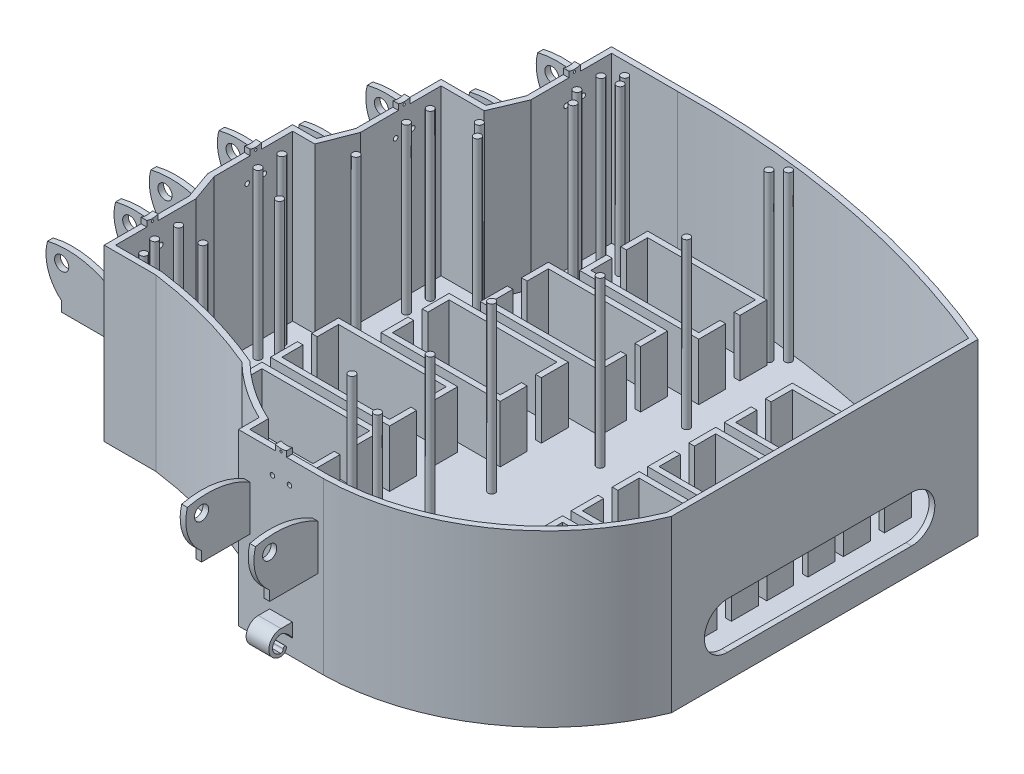
SolidWorks part; units mm, degrees
ref_plane "Front Plane" through (0, 0, 0) normal (0, 0, 1) x (1, 0, 0)
ref_plane "Top Plane" through (0, 0, 0) normal (0, 1, 0) x (1, 0, 0)
ref_plane "Right Plane" through (0, 0, 0) normal (1, 0, 0) x (0, 0, -1)
ref_plane "Palm Side Plane" through (0, 38.1, 0) normal (0, 1, 0) x (1, 0, 0)
ref_plane "Left Side Plane" through (0, 0, 63.5) normal (0, 0, 1) x (1, 0, 0)
ref_plane "Top Side Plane" through (-69.85, 0, 0) normal (1, 0, 0) x (0, 0, -1)
ref_plane "Wrist Plane" through (62.9138, 0, 0) normal (1, 0, 0) x (0, 0, -1)
sketch "Hand Direction Arrow" plane through (0, 38.1, 0) normal (0, 1, 0) x (1, 0, 0)
  line L0 (49.8191, -114.0829) -> (-36.738, -114.0829) construction
  line L1 (-36.738, -114.0829) -> (-22.4792, -131.555) construction
  line L2 (-36.738, -114.0829) -> (-22.4792, -99.8241) construction
sketch "Sketch2" plane through (0, 0, 0) normal (0, 1, 0) x (1, 0, 0)
  line L5 (-69.85, -63.5) -> (69.85, 63.5) construction
  line L6 (-69.85, 63.5) -> (69.85, -63.5) construction
  line L7 (-20.7784, 52.7587) -> (-36.189, 52.7587)
  line L8 (-36.189, 52.7587) -> (-36.189, 33.7087)
  line L9 (-42.9594, -42.4913) -> (-54.5039, -42.4913)
  line L10 (-54.5039, -42.4913) -> (-54.5039, -23.4413)
  line L11 (-54.5039, -23.4413) -> (-56.7676, -17.0913)
  line L12 (-51.4171, 1.9587) -> (-48.9477, 8.3087)
  line L14 (-56.7676, -17.0913) -> (-56.7676, 1.9587)
  line L15 (-56.7676, 1.9587) -> (-51.4171, 1.9587)
  line L16 (-38.8642, 27.3587) -> (-36.189, 33.7087)
  line L19 (15.3118, -63.2103) -> (-3.7382, -63.2103)
  line L20 (-3.7382, -63.2103) -> (-3.7382, -58.593)
  line L21 (61.5724, -31.5884) -> (61.5724, 37.0553)
  line L22 (-48.9477, 8.3087) -> (-48.9477, 27.3587)
  line L23 (-48.9477, 27.3587) -> (-38.8642, 27.3587)
  arc A0 (61.5724, 37.0553) -> (-20.7784, 52.7587) centre (-16.6219, -149.2259) ccw
  arc A2 (-42.9594, -42.4913) -> (-16.4221, -49.7553) centre (-56.8306, -145.2734) cw
  arc A5 (-3.7382, -58.593) -> (-16.4221, -49.7553) centre (16.7508, -15.6666) cw
  arc A6 (15.3118, -63.2103) -> (61.5724, -31.5884) centre (14.5642, -12.4678) ccw
  point P0 (0, 0)
  dimension "D1" = 19.05
  dimension "D2" = 19.05
  dimension "D3" = 19.05
  dimension "D4" = 19.05
  dimension "D5" = 19.05
  dimension "D6" = 6.35
  dimension "D7" = 6.35
extrude "Boss-Extrude1" add sketch "Sketch2" along normal blind 38.1
sketch "Sketch3" plane through (0, 38.1, 0) normal (0, 1, 0) x (1, 0, 0)
  line L5 (-68.58, -62.23) -> (68.58, 62.23) construction
  line L6 (-68.58, 62.23) -> (68.58, -62.23) construction
  line L7 (-20.1932, 51.4997) -> (-34.919, 51.4997)
  line L8 (-34.919, 51.4997) -> (-34.919, 33.4521)
  line L10 (-36.189, 52.7587) -> (-36.189, 33.7087) construction
  line L11 (-54.5039, -23.4413) -> (-54.5039, -42.4913) construction
  line L12 (-42.8744, -41.2213) -> (-53.2339, -41.2213)
  line L13 (-53.2339, -41.2213) -> (-53.2339, -23.2217)
  line L18 (-55.4976, -16.8717) -> (-55.4976, 0.6887)
  line L19 (-55.4976, 0.6887) -> (-50.5484, 0.6887)
  line L22 (-56.7676, 1.9587) -> (-56.7676, -17.0913) construction
  line L23 (-51.4171, 1.9587) -> (-56.7676, 1.9587) construction
  line L24 (-47.6777, 8.0704) -> (-47.6777, 26.0887)
  line L25 (-47.6777, 26.0887) -> (-38.0211, 26.0887)
  line L26 (-48.9477, 27.3587) -> (-48.9477, 8.3087) construction
  line L27 (-38.8642, 27.3587) -> (-48.9477, 27.3587) construction
  line L28 (-38.0211, 26.0887) -> (-34.919, 33.4521)
  line L29 (-36.189, 33.7087) -> (-38.8642, 27.3587) construction
  line L30 (-50.5484, 0.6887) -> (-47.6777, 8.0704)
  line L31 (-54.5039, -42.4913) -> (-42.9594, -42.4913) construction
  line L32 (-53.2339, -23.2217) -> (-55.4976, -16.8717)
  line L33 (-56.7676, -17.0913) -> (-54.5039, -23.4413) construction
  line L34 (-48.9477, 8.3087) -> (-51.4171, 1.9587) construction
  line L35 (15.3312, -61.9403) -> (-2.4682, -61.9403)
  line L36 (-2.4682, -61.9403) -> (-2.4682, -57.7843)
  line L37 (-3.7382, -58.593) -> (-3.7382, -63.2103) construction
  line L38 (-3.7382, -63.2103) -> (15.3118, -63.2103) construction
  line L39 (60.3024, -31.3395) -> (60.3024, 36.2091)
  line L40 (61.5724, -31.5884) -> (61.5724, 37.0553) construction
  arc A1 (-20.1932, 51.4997) -> (60.3024, 36.2091) centre (-16.6219, -149.2259) cw
  arc A4 (61.5724, 37.0553) -> (-20.7784, 52.7587) centre (-16.6219, -149.2259) ccw construction
  arc A5 (15.3118, -63.2103) -> (61.5724, -31.5884) centre (14.5642, -12.4678) ccw construction
  arc A8 (-42.8744, -41.2213) -> (-15.7053, -48.6798) centre (-56.8306, -145.2734) cw
  arc A9 (-16.4221, -49.7553) -> (-42.9594, -42.4913) centre (-56.8306, -145.2734) ccw construction
  arc A12 (15.3312, -61.9403) -> (60.3024, -31.3395) centre (14.5642, -12.4678) ccw
  arc A13 (-2.4682, -57.7843) -> (-15.7053, -48.6798) centre (16.7508, -15.6666) cw
  arc A14 (-16.4221, -49.7553) -> (-3.7382, -58.593) centre (16.7508, -15.6666) ccw construction
  point P0 (0, 0)
  point P6 (-45.5127, -25.7954)
  point P29 (-45.5127, -25.7954)
  point P52 (-54.0923, 1.9587)
  dimension "D2" = 1.27
  dimension "D3" = 1.27
  dimension "D5" = 1.27
  dimension "D6" = 1.27
  dimension "D8" = 1.27
  dimension "D4" = 1.27
  dimension "D7" = 1.27
  dimension "D9" = 1.27
  dimension "D10" = 1.27
  dimension "D11" = 1.27
  dimension "D12" = 1.27
  dimension "D13" = 1.27
  dimension "D14" = 1.27
  dimension "D15" = 1.27
  dimension "D16" = 1.27
  dimension "D17" = 1.27
extrude "Cut-Extrude1" cut sketch "Sketch3" against normal blind 36.83
sketch "Sketch6" plane through (0, 0, 0) normal (0, 1, 0) x (1, 0, 0)
  line L0 (-38.2959, -32.597) -> (-37.0259, -32.597)
  line L5 (-63.3937, -68.1577) -> (73.7663, 56.3023) construction
  line L6 (-64.5742, 57.9506) -> (72.5858, -66.5094) construction
  line L7 (-12.8959, -37.3595) -> (-37.0259, -37.3595)
  line L8 (-12.8959, -37.3595) -> (-12.8959, -32.597)
  line L9 (-12.8959, -24.6595) -> (-37.0259, -24.6595)
  line L10 (-37.0259, -37.3595) -> (-37.0259, -32.597)
  line L11 (-12.8959, -37.3595) -> (-37.0259, -24.6595) construction
  line L12 (-12.8959, -24.6595) -> (-37.0259, -37.3595) construction
  line L13 (-11.6259, -38.6295) -> (-38.2959, -38.6295)
  line L14 (-11.6259, -38.6295) -> (-11.6259, -32.597)
  line L15 (-11.6259, -23.3895) -> (-38.2959, -23.3895)
  line L16 (-38.2959, -38.6295) -> (-38.2959, -32.597)
  line L17 (-11.6259, -38.6295) -> (-38.2959, -23.3895) construction
  line L18 (-11.6259, -23.3895) -> (-38.2959, -38.6295) construction
  line L19 (-38.2959, -29.422) -> (-37.0259, -29.422)
  line L20 (-38.2959, -29.422) -> (-38.2959, -23.3895)
  line L21 (-37.0259, -29.422) -> (-37.0259, -24.6595)
  line L22 (-12.8959, -32.597) -> (-11.6259, -32.597)
  line L23 (-12.8959, -29.422) -> (-11.6259, -29.422)
  line L24 (-12.8959, -29.422) -> (-12.8959, -24.6595)
  line L25 (-11.6259, -29.422) -> (-11.6259, -23.3895)
  point P0 (5.5042, -5.6391)
  point P6 (-24.9609, -31.0095)
  point P29 (-24.9609, -31.0095)
  dimension "D6" = 1.27
  dimension "D7" = 1.27
  dimension "D9" = 12.7
  dimension "D10" = 24.13
  dimension "D11" = 4.7625
  dimension "D12" = 4.7625
  dimension "D13" = 4.7625
  dimension "D14" = 4.7625
extrude "Boss-Extrude2" add sketch "Sketch6" along normal blind 13.97
sketch "Sketch7" plane through (0, 0, 0) normal (0, 1, 0) x (1, 0, 0)
  line L0 (-38.2959, -15.452) -> (-37.0259, -15.452)
  line L5 (-11.6259, -23.3895) -> (-38.2959, -23.3895) construction
  line L6 (-38.2959, -23.3895) -> (-38.2959, -29.422) construction
  line L7 (-12.8959, -20.2145) -> (-37.0259, -20.2145)
  line L8 (-12.8959, -20.2145) -> (-12.8959, -15.452)
  line L9 (-12.8959, -7.5145) -> (-37.0259, -7.5145)
  line L10 (-37.0259, -20.2145) -> (-37.0259, -15.452)
  line L11 (-12.8959, -20.2145) -> (-37.0259, -7.5145) construction
  line L12 (-12.8959, -7.5145) -> (-37.0259, -20.2145) construction
  line L13 (-11.6259, -21.4845) -> (-38.2959, -21.4845)
  line L14 (-11.6259, -21.4845) -> (-11.6259, -15.452)
  line L15 (-11.6259, -6.2445) -> (-38.2959, -6.2445)
  line L16 (-38.2959, -21.4845) -> (-38.2959, -15.452)
  line L17 (-11.6259, -21.4845) -> (-38.2959, -6.2445) construction
  line L18 (-11.6259, -6.2445) -> (-38.2959, -21.4845) construction
  line L19 (-38.2959, -12.277) -> (-37.0259, -12.277)
  line L20 (-38.2959, -12.277) -> (-38.2959, -6.2445)
  line L21 (-37.0259, -12.277) -> (-37.0259, -7.5145)
  line L22 (-12.8959, -15.452) -> (-11.6259, -15.452)
  line L23 (-12.8959, -12.277) -> (-11.6259, -12.277)
  line L24 (-12.8959, -12.277) -> (-12.8959, -7.5145)
  line L25 (-11.6259, -12.277) -> (-11.6259, -6.2445)
  point P0 (-14.8998, -5.4903)
  point P6 (-24.9609, -13.8645)
  point P29 (-24.9609, -13.8645)
  dimension "D2" = 1.905
  dimension "D3" = 0
  dimension "D6" = 1.27
  dimension "D7" = 1.27
  dimension "D9" = 12.7
  dimension "D10" = 24.13
  dimension "D11" = 4.7625
  dimension "D12" = 4.7625
  dimension "D13" = 4.7625
  dimension "D14" = 4.7625
extrude "Boss-Extrude3" add sketch "Sketch7" along normal blind 13.97
sketch "Sketch15" plane through (0, 0, 0) normal (0, -1, 0) x (1, 0, 0)
  line L0 (-30.6759, -4.868) -> (-29.4059, -4.868)
  line L5 (-11.6259, 6.2445) -> (-38.2959, 6.2445) construction
  line L6 (-38.2959, 6.2445) -> (-38.2959, 12.277) construction
  line L7 (-5.2759, -9.6305) -> (-29.4059, -9.6305)
  line L8 (-5.2759, -9.6305) -> (-5.2759, -4.868)
  line L9 (-5.2759, 3.0695) -> (-29.4059, 3.0695)
  line L10 (-29.4059, -9.6305) -> (-29.4059, -4.868)
  line L11 (-5.2759, -9.6305) -> (-29.4059, 3.0695) construction
  line L12 (-5.2759, 3.0695) -> (-29.4059, -9.6305) construction
  line L13 (-4.0059, -10.9005) -> (-30.6759, -10.9005)
  line L14 (-4.0059, -10.9005) -> (-4.0059, -4.868)
  line L15 (-4.0059, 4.3395) -> (-30.6759, 4.3395)
  line L16 (-30.6759, -10.9005) -> (-30.6759, -4.868)
  line L17 (-4.0059, -10.9005) -> (-30.6759, 4.3395) construction
  line L18 (-4.0059, 4.3395) -> (-30.6759, -10.9005) construction
  line L19 (-30.6759, -1.693) -> (-29.4059, -1.693)
  line L20 (-30.6759, -1.693) -> (-30.6759, 4.3395)
  line L21 (-29.4059, -1.693) -> (-29.4059, 3.0695)
  line L22 (-5.2759, -4.868) -> (-4.0059, -4.868)
  line L23 (-5.2759, -1.693) -> (-4.0059, -1.693)
  line L24 (-5.2759, -1.693) -> (-5.2759, 3.0695)
  line L25 (-4.0059, -1.693) -> (-4.0059, 4.3395)
  point P0 (-6.5637, 8.998)
  point P6 (-17.3409, -3.2805)
  point P29 (-17.3409, -3.2805)
  dimension "D2" = 1.905
  dimension "D3" = 7.62
  dimension "D6" = 1.27
  dimension "D7" = 1.27
  dimension "D9" = 12.7
  dimension "D10" = 24.13
  dimension "D11" = 4.7625
  dimension "D12" = 4.7625
  dimension "D13" = 4.7625
  dimension "D14" = 4.7625
extrude "Boss-Extrude4" add sketch "Sketch15" against normal blind 13.97
sketch "Sketch16" plane through (0, 0, 0) normal (0, -1, 0) x (1, 0, 0)
  line L0 (-25.5959, -22.013) -> (-24.3259, -22.013)
  line L5 (-30.6759, -10.9005) -> (-4.0059, -10.9005) construction
  line L6 (-30.6759, -4.868) -> (-30.6759, -10.9005) construction
  line L7 (-0.1959, -26.7755) -> (-24.3259, -26.7755)
  line L8 (-0.1959, -26.7755) -> (-0.1959, -22.013)
  line L9 (-0.1959, -14.0755) -> (-24.3259, -14.0755)
  line L10 (-24.3259, -26.7755) -> (-24.3259, -22.013)
  line L11 (-0.1959, -26.7755) -> (-24.3259, -14.0755) construction
  line L12 (-0.1959, -14.0755) -> (-24.3259, -26.7755) construction
  line L13 (1.0741, -28.0455) -> (-25.5959, -28.0455)
  line L14 (1.0741, -28.0455) -> (1.0741, -22.013)
  line L15 (1.0741, -12.8055) -> (-25.5959, -12.8055)
  line L16 (-25.5959, -28.0455) -> (-25.5959, -22.013)
  line L17 (1.0741, -28.0455) -> (-25.5959, -12.8055) construction
  line L18 (1.0741, -12.8055) -> (-25.5959, -28.0455) construction
  line L19 (-25.5959, -18.838) -> (-24.3259, -18.838)
  line L20 (-25.5959, -18.838) -> (-25.5959, -12.8055)
  line L21 (-24.3259, -18.838) -> (-24.3259, -14.0755)
  line L22 (-0.1959, -22.013) -> (1.0741, -22.013)
  line L23 (-0.1959, -18.838) -> (1.0741, -18.838)
  line L24 (-0.1959, -18.838) -> (-0.1959, -14.0755)
  line L25 (1.0741, -18.838) -> (1.0741, -12.8055)
  point P0 (1.9027, -6.9539)
  point P6 (-12.2609, -20.4255)
  point P29 (-12.2609, -20.4255)
  dimension "D2" = 1.905
  dimension "D3" = 5.08
  dimension "D6" = 1.27
  dimension "D7" = 1.27
  dimension "D9" = 12.7
  dimension "D10" = 24.13
  dimension "D11" = 4.7625
  dimension "D12" = 4.7625
  dimension "D13" = 4.7625
  dimension "D14" = 4.7625
extrude "Boss-Extrude5" add sketch "Sketch16" against normal blind 13.97
sketch "Sketch17" plane through (0, 0, 0) normal (0, -1, 0) x (1, 0, 0)
  line L0 (-20.5159, -39.158) -> (-19.2459, -39.158)
  line L5 (-25.5959, -28.0455) -> (1.0741, -28.0455) construction
  line L6 (-25.5959, -22.013) -> (-25.5959, -28.0455) construction
  line L7 (4.8841, -43.9205) -> (-19.2459, -43.9205)
  line L8 (4.8841, -43.9205) -> (4.8841, -39.158)
  line L9 (4.8841, -31.2205) -> (-19.2459, -31.2205)
  line L10 (-19.2459, -43.9205) -> (-19.2459, -39.158)
  line L11 (4.8841, -43.9205) -> (-19.2459, -31.2205) construction
  line L12 (4.8841, -31.2205) -> (-19.2459, -43.9205) construction
  line L13 (6.1541, -45.1905) -> (-20.5159, -45.1905)
  line L14 (6.1541, -45.1905) -> (6.1541, -39.158)
  line L15 (6.1541, -29.9505) -> (-20.5159, -29.9505)
  line L16 (-20.5159, -45.1905) -> (-20.5159, -39.158)
  line L17 (6.1541, -45.1905) -> (-20.5159, -29.9505) construction
  line L18 (6.1541, -29.9505) -> (-20.5159, -45.1905) construction
  line L19 (-20.5159, -35.983) -> (-19.2459, -35.983)
  line L20 (-20.5159, -35.983) -> (-20.5159, -29.9505)
  line L21 (-19.2459, -35.983) -> (-19.2459, -31.2205)
  line L22 (4.8841, -39.158) -> (6.1541, -39.158)
  line L23 (4.8841, -35.983) -> (6.1541, -35.983)
  line L24 (4.8841, -35.983) -> (4.8841, -31.2205)
  line L25 (6.1541, -35.983) -> (6.1541, -29.9505)
  point P0 (6.1079, -24.4951)
  point P6 (-7.1809, -37.5705)
  point P29 (-7.1809, -37.5705)
  dimension "D2" = 1.905
  dimension "D3" = 5.08
  dimension "D6" = 1.27
  dimension "D7" = 1.27
  dimension "D9" = 12.7
  dimension "D10" = 24.13
  dimension "D11" = 4.7625
  dimension "D12" = 4.7625
  dimension "D13" = 4.7625
  dimension "D14" = 4.7625
extrude "Boss-Extrude6" add sketch "Sketch17" against normal blind 13.97
sketch "Sketch18" plane through (0, 0, 0) normal (0, -1, 0) x (1, 0, 0)
  line L0 (14.981, 42.6949) -> (16.251, 42.6949)
  line L7 (40.381, 37.9324) -> (16.251, 37.9324)
  line L8 (40.381, 37.9324) -> (40.381, 42.6949)
  line L9 (40.381, 50.6324) -> (16.251, 50.6324)
  line L10 (16.251, 37.9324) -> (16.251, 42.6949)
  line L11 (40.381, 37.9324) -> (16.251, 50.6324) construction
  line L12 (40.381, 50.6324) -> (16.251, 37.9324) construction
  line L13 (41.651, 36.6624) -> (14.981, 36.6624)
  line L14 (41.651, 36.6624) -> (41.651, 42.6949)
  line L15 (41.651, 51.9024) -> (14.981, 51.9024)
  line L16 (14.981, 36.6624) -> (14.981, 42.6949)
  line L17 (41.651, 36.6624) -> (14.981, 51.9024) construction
  line L18 (41.651, 51.9024) -> (14.981, 36.6624) construction
  line L19 (14.981, 45.8699) -> (16.251, 45.8699)
  line L20 (14.981, 45.8699) -> (14.981, 51.9024)
  line L21 (16.251, 45.8699) -> (16.251, 50.6324)
  line L22 (40.381, 42.6949) -> (41.651, 42.6949)
  line L23 (40.381, 45.8699) -> (41.651, 45.8699)
  line L24 (40.381, 45.8699) -> (40.381, 50.6324)
  line L25 (41.651, 45.8699) -> (41.651, 51.9024)
  point P0 (43.5107, 54.1626)
  point P6 (28.316, 44.2824)
  point P29 (28.316, 44.2824)
  dimension "D6" = 1.27
  dimension "D7" = 1.27
  dimension "D9" = 12.7
  dimension "D10" = 24.13
  dimension "D11" = 4.7625
  dimension "D12" = 4.7625
  dimension "D13" = 4.7625
  dimension "D14" = 4.7625
extrude "Boss-Extrude7" add sketch "Sketch18" against normal blind 13.97
sketch "Sketch19" plane through (0, 0, 0) normal (0, -1, 0) x (1, 0, 0)
  line L0 (25.141, 25.5499) -> (26.411, 25.5499)
  line L5 (14.981, 36.6624) -> (41.651, 36.6624) construction
  line L6 (14.981, 42.6949) -> (14.981, 36.6624) construction
  line L7 (50.541, 20.7874) -> (26.411, 20.7874)
  line L8 (50.541, 20.7874) -> (50.541, 25.5499)
  line L9 (50.541, 33.4874) -> (26.411, 33.4874)
  line L10 (26.411, 20.7874) -> (26.411, 25.5499)
  line L11 (50.541, 20.7874) -> (26.411, 33.4874) construction
  line L12 (50.541, 33.4874) -> (26.411, 20.7874) construction
  line L13 (51.811, 19.5174) -> (25.141, 19.5174)
  line L14 (51.811, 19.5174) -> (51.811, 25.5499)
  line L15 (51.811, 34.7574) -> (25.141, 34.7574)
  line L16 (25.141, 19.5174) -> (25.141, 25.5499)
  line L17 (51.811, 19.5174) -> (25.141, 34.7574) construction
  line L18 (51.811, 34.7574) -> (25.141, 19.5174) construction
  line L19 (25.141, 28.7249) -> (26.411, 28.7249)
  line L20 (25.141, 28.7249) -> (25.141, 34.7574)
  line L21 (26.411, 28.7249) -> (26.411, 33.4874)
  line L22 (50.541, 25.5499) -> (51.811, 25.5499)
  line L23 (50.541, 28.7249) -> (51.811, 28.7249)
  line L24 (50.541, 28.7249) -> (50.541, 33.4874)
  line L25 (51.811, 28.7249) -> (51.811, 34.7574)
  point P0 (52.4146, 37.8023)
  point P6 (38.476, 27.1374)
  point P29 (38.476, 27.1374)
  dimension "D2" = 1.905
  dimension "D3" = 10.16
  dimension "D6" = 1.27
  dimension "D7" = 1.27
  dimension "D9" = 12.7
  dimension "D10" = 24.13
  dimension "D11" = 4.7625
  dimension "D12" = 4.7625
  dimension "D13" = 4.7625
  dimension "D14" = 4.7625
extrude "Boss-Extrude8" add sketch "Sketch19" against normal blind 13.97
sketch "Sketch20" plane through (0, 0, 0) normal (0, -1, 0) x (1, 0, 0)
  line L0 (25.141, 8.4049) -> (26.411, 8.4049)
  line L5 (25.141, 25.5499) -> (25.141, 19.5174) construction
  line L6 (25.141, 19.5174) -> (51.811, 19.5174) construction
  line L7 (50.541, 3.6424) -> (26.411, 3.6424)
  line L8 (50.541, 3.6424) -> (50.541, 8.4049)
  line L9 (50.541, 16.3424) -> (26.411, 16.3424)
  line L10 (26.411, 3.6424) -> (26.411, 8.4049)
  line L11 (50.541, 3.6424) -> (26.411, 16.3424) construction
  line L12 (50.541, 16.3424) -> (26.411, 3.6424) construction
  line L13 (51.811, 2.3724) -> (25.141, 2.3724)
  line L14 (51.811, 2.3724) -> (51.811, 8.4049)
  line L15 (51.811, 17.6124) -> (25.141, 17.6124)
  line L16 (25.141, 2.3724) -> (25.141, 8.4049)
  line L17 (51.811, 2.3724) -> (25.141, 17.6124) construction
  line L18 (51.811, 17.6124) -> (25.141, 2.3724) construction
  line L19 (25.141, 11.5799) -> (26.411, 11.5799)
  line L20 (25.141, 11.5799) -> (25.141, 17.6124)
  line L21 (26.411, 11.5799) -> (26.411, 16.3424)
  line L22 (50.541, 8.4049) -> (51.811, 8.4049)
  line L23 (50.541, 11.5799) -> (51.811, 11.5799)
  line L24 (50.541, 11.5799) -> (50.541, 16.3424)
  line L25 (51.811, 11.5799) -> (51.811, 17.6124)
  point P0 (54.8865, 20.8211)
  point P6 (38.476, 9.9924)
  point P29 (38.476, 9.9924)
  dimension "D2" = 0
  dimension "D3" = 1.905
  dimension "D6" = 1.27
  dimension "D7" = 1.27
  dimension "D9" = 12.7
  dimension "D10" = 24.13
  dimension "D11" = 4.7625
  dimension "D12" = 4.7625
  dimension "D13" = 4.7625
  dimension "D14" = 4.7625
extrude "Boss-Extrude9" add sketch "Sketch20" against normal blind 13.97
sketch "Sketch21" plane through (0, 0, 0) normal (0, -1, 0) x (1, 0, 0)
  line L0 (25.141, -8.7401) -> (26.411, -8.7401)
  line L5 (25.141, 2.3724) -> (51.811, 2.3724) construction
  line L6 (25.141, 8.4049) -> (25.141, 2.3724) construction
  line L7 (50.541, -13.5026) -> (26.411, -13.5026)
  line L8 (50.541, -13.5026) -> (50.541, -8.7401)
  line L9 (50.541, -0.8026) -> (26.411, -0.8026)
  line L10 (26.411, -13.5026) -> (26.411, -8.7401)
  line L11 (50.541, -13.5026) -> (26.411, -0.8026) construction
  line L12 (50.541, -0.8026) -> (26.411, -13.5026) construction
  line L13 (51.811, -14.7726) -> (25.141, -14.7726)
  line L14 (51.811, -14.7726) -> (51.811, -8.7401)
  line L15 (51.811, 0.4674) -> (25.141, 0.4674)
  line L16 (25.141, -14.7726) -> (25.141, -8.7401)
  line L17 (51.811, -14.7726) -> (25.141, 0.4674) construction
  line L18 (51.811, 0.4674) -> (25.141, -14.7726) construction
  line L19 (25.141, -5.5651) -> (26.411, -5.5651)
  line L20 (25.141, -5.5651) -> (25.141, 0.4674)
  line L21 (26.411, -5.5651) -> (26.411, -0.8026)
  line L22 (50.541, -8.7401) -> (51.811, -8.7401)
  line L23 (50.541, -5.5651) -> (51.811, -5.5651)
  line L24 (50.541, -5.5651) -> (50.541, -0.8026)
  line L25 (51.811, -5.5651) -> (51.811, 0.4674)
  point P0 (52.1156, 3.8173)
  point P6 (38.476, -7.1526)
  point P29 (38.476, -7.1526)
  dimension "D2" = 1.905
  dimension "D3" = 0
  dimension "D6" = 1.27
  dimension "D7" = 1.27
  dimension "D9" = 12.7
  dimension "D10" = 24.13
  dimension "D11" = 4.7625
  dimension "D12" = 4.7625
  dimension "D13" = 4.7625
  dimension "D14" = 4.7625
extrude "Boss-Extrude10" add sketch "Sketch21" against normal blind 13.97
sketch "Sketch22" plane through (0, 0, 0) normal (0, -1, 0) x (1, 0, 0)
  line L0 (25.141, -25.8851) -> (26.411, -25.8851)
  line L5 (25.141, -14.7726) -> (51.811, -14.7726) construction
  line L6 (25.141, -8.7401) -> (25.141, -14.7726) construction
  line L7 (50.541, -30.6476) -> (26.411, -30.6476)
  line L8 (50.541, -30.6476) -> (50.541, -25.8851)
  line L9 (50.541, -17.9476) -> (26.411, -17.9476)
  line L10 (26.411, -30.6476) -> (26.411, -25.8851)
  line L11 (50.541, -30.6476) -> (26.411, -17.9476) construction
  line L12 (50.541, -17.9476) -> (26.411, -30.6476) construction
  line L13 (51.811, -31.9176) -> (25.141, -31.9176)
  line L14 (51.811, -31.9176) -> (51.811, -25.8851)
  line L15 (51.811, -16.6776) -> (25.141, -16.6776)
  line L16 (25.141, -31.9176) -> (25.141, -25.8851)
  line L17 (51.811, -31.9176) -> (25.141, -16.6776) construction
  line L18 (51.811, -16.6776) -> (25.141, -31.9176) construction
  line L19 (25.141, -22.7101) -> (26.411, -22.7101)
  line L20 (25.141, -22.7101) -> (25.141, -16.6776)
  line L21 (26.411, -22.7101) -> (26.411, -17.9476)
  line L22 (50.541, -25.8851) -> (51.811, -25.8851)
  line L23 (50.541, -22.7101) -> (51.811, -22.7101)
  line L24 (50.541, -22.7101) -> (50.541, -17.9476)
  line L25 (51.811, -22.7101) -> (51.811, -16.6776)
  point P0 (57.6091, -14.277)
  point P6 (38.476, -24.2976)
  point P29 (38.476, -24.2976)
  dimension "D2" = 1.905
  dimension "D3" = 0
  dimension "D6" = 1.27
  dimension "D7" = 1.27
  dimension "D9" = 12.7
  dimension "D10" = 24.13
  dimension "D11" = 4.7625
  dimension "D12" = 4.7625
  dimension "D13" = 4.7625
  dimension "D14" = 4.7625
extrude "Boss-Extrude11" add sketch "Sketch22" against normal blind 13.97
sketch "Sketch25" plane through (0, 0, 63.5) normal (0, 0, 1) x (1, 0, 0)
  line L0 (15.3118, 38.1) -> (15.3118, 0) construction
  line L1 (49.8191, 38.1) -> (-36.738, 38.1) construction
  line L6 (-3.7382, 38.1) -> (-3.7382, 0) construction
  circle A0 centre (7.6918, 33.02) radius 0.508
  circle A1 centre (3.8818, 33.02) radius 0.508
  dimension "D3" = 7.62
  dimension "D1" = 5.08
  dimension "D2" = 5.08
  dimension "D4" = 7.62
extrude "Thumb Holes" cut sketch "Sketch25" against normal blind 12.7
sketch "Sketch31" plane through (-69.85, 0, 0) normal (1, 0, 0) x (0, 0, -1)
  line L0 (-23.4413, 38.1) -> (-23.4413, 0) construction
  line L1 (-23.4413, 38.1) -> (-42.4913, 38.1) construction
  line L2 (-42.4913, 38.1) -> (-42.4913, 0) construction
  circle A0 centre (-31.0613, 33.02) radius 0.508
  circle A1 centre (-34.8713, 33.02) radius 0.508
  dimension "D1" = 7.62
  dimension "D2" = 5.08
  dimension "D3" = 5.08
  dimension "D4" = 7.62
extrude "Index Finger Holes" cut sketch "Sketch31" along normal blind 17.018
sketch "Sketch32" plane through (-69.85, 0, 0) normal (1, 0, 0) x (0, 0, -1)
  line L0 (1.9587, 38.1) -> (1.9587, 0) construction
  line L1 (-17.0913, 38.1) -> (-17.0913, 0) construction
  line L2 (1.9587, 38.1) -> (-17.0913, 38.1) construction
  circle A0 centre (-9.4713, 33.02) radius 0.508
  circle A1 centre (-5.6613, 33.02) radius 0.508
  dimension "D1" = 7.62
  dimension "D2" = 7.62
  dimension "D3" = 5.08
  dimension "D4" = 5.08
extrude "Middle Finger Holes" cut sketch "Sketch32" along normal blind 15.24
sketch "Sketch33" plane through (-69.85, 0, 0) normal (1, 0, 0) x (0, 0, -1)
  line L0 (27.3587, 38.1) -> (27.3587, 0) construction
  line L1 (27.3587, 38.1) -> (8.3087, 38.1) construction
  line L2 (8.3087, 38.1) -> (8.3087, 0) construction
  circle A0 centre (15.9287, 33.02) radius 0.508
  circle A1 centre (19.7387, 33.02) radius 0.508
  dimension "D1" = 7.62
  dimension "D2" = 5.08
  dimension "D3" = 5.08
  dimension "D4" = 7.62
extrude "Ring Finger Holes" cut sketch "Sketch33" along normal blind 22.86
sketch "Sketch34" plane through (-69.85, 0, 0) normal (1, 0, 0) x (0, 0, -1)
  line L0 (52.7587, 38.1) -> (33.7087, 38.1) construction
  line L1 (52.8014, 0) -> (52.8014, 38.1) construction
  line L2 (33.7087, 38.1) -> (33.7087, 0) construction
  circle A0 centre (41.3287, 33.02) radius 0.508
  circle A1 centre (45.1814, 33.02) radius 0.508
  dimension "D1" = 5.08
  dimension "D2" = 7.62
  dimension "D3" = 7.62
  dimension "D4" = 5.08
extrude "Pinky Finger Holes" cut sketch "Sketch34" along normal blind 35.56
sketch "Sketch26" plane through (0, 38.1, 0) normal (0, 1, 0) x (1, 0, 0)
  line L0 (-1.8504, -40.4696) -> (-48.4714, -40.4696) construction
  line L1 (8.3049, 24.2976) -> (8.3049, 48.6758) construction
  line L2 (6.0975, 7.1526) -> (6.0975, 46.5196) construction
  line L3 (-1.0566, -9.9924) -> (-1.0566, -39.6758) construction
  line L4 (-53.2339, -23.2217) -> (-53.2339, -41.2213) construction
  line L5 (-37.0259, -15.452) -> (-38.2959, -15.452) construction
  line L6 (14.981, -45.8699) -> (16.251, -45.8699) construction
  line L7 (25.141, -28.7249) -> (26.411, -28.7249) construction
  line L8 (25.141, -11.5799) -> (26.411, -11.5799) construction
  line L9 (25.141, 5.5651) -> (26.411, 5.5651) construction
  line L10 (25.141, 22.7101) -> (26.411, 22.7101) construction
  line L11 (-30.6759, 1.693) -> (-29.4059, 1.693) construction
  line L12 (-25.5959, 18.838) -> (-24.3259, 18.838) construction
  line L13 (-20.5159, 35.983) -> (-19.2459, 35.983) construction
  line L14 (5.3037, 47.3134) -> (-28.0099, 47.3134) construction
  line L15 (7.5112, 49.4695) -> (-29.1533, 49.4695) construction
  line L16 (-53.2339, -23.2217) -> (-53.2339, -41.2213) construction
  line L17 (-55.4976, 0.6887) -> (-55.4976, -16.8717) construction
  line L18 (-47.6777, 26.0887) -> (-47.6777, 8.0704) construction
  line L19 (-47.6777, 26.0887) -> (-47.6777, 8.0704) construction
  line L20 (-34.919, 51.4997) -> (-34.919, 33.4521) construction
  line L21 (-34.919, 51.4997) -> (-34.919, 33.4521) construction
  line L22 (-37.0259, -32.597) -> (-38.2959, -32.597) construction
  line L23 (-49.2652, -39.6758) -> (-49.2652, -35.6333) construction
  circle A0 centre (8.4538, -44.2824) radius 0.7937
  circle A1 centre (3.1198, -27.1374) radius 0.7937
  circle A2 centre (-0.2629, -9.9924) radius 0.7937
  circle A3 centre (6.8912, 7.1526) radius 0.7938
  circle A4 centre (9.0987, 24.2976) radius 0.7937
  circle A5 centre (-1.8504, -39.6758) radius 0.7938
  circle A6 centre (7.5112, 48.6758) radius 0.7938
  circle A7 centre (5.3037, 46.5196) radius 0.7938
  circle A8 centre (-48.4714, -39.6758) radius 0.7937
  circle A9 centre (-52.3226, -10.2333) radius 0.7937
  circle A10 centre (-52.3226, -4.8993) radius 0.7937
  circle A11 centre (-43.8931, -13.8645) radius 0.7937
  circle A12 centre (-43.8931, 3.2805) radius 0.7937
  circle A13 centre (-33.8741, 20.4255) radius 0.7937
  circle A14 centre (-44.5027, 15.1667) radius 0.7937
  circle A15 centre (-29.6038, 37.5705) radius 0.7937
  circle A16 centre (-36.3066, 23.2954) radius 0.7937
  circle A17 centre (-44.5027, 20.5007) radius 0.7937
  circle A18 centre (-28.0099, 46.5196) radius 0.7937
  circle A19 centre (-29.1533, 48.6758) radius 0.7938
  circle A20 centre (-31.744, 40.5667) radius 0.7937
  circle A21 centre (-31.744, 45.9434) radius 0.7937
  circle A22 centre (-50.0589, -35.6333) radius 0.7937
  circle A23 centre (-50.0589, -30.2993) radius 0.7937
  circle A24 centre (-43.8931, -31.0095) radius 0.7937
  dimension "D6" = 0.254
  dimension "D7" = 0.254
  dimension "D14" = 1.5875
  dimension "D15" = 1.5875
  dimension "D16" = 1.5875
  dimension "D17" = 1.5875
  dimension "D18" = 1.5875
  dimension "D19" = 1.5875
  dimension "D20" = 1.5875
  dimension "D21" = 1.5875
  dimension "D22" = 1.5875
  dimension "D23" = 1.5875
  dimension "D24" = 1.5875
  dimension "D25" = 1.5875
  dimension "D26" = 1.5875
  dimension "D27" = 1.5875
  dimension "D28" = 1.5875
  dimension "D29" = 1.5875
  dimension "D30" = 1.5875
  dimension "D31" = 1.5875
  dimension "D32" = 1.5875
  dimension "D33" = 1.5875
  dimension "D34" = 1.5875
  dimension "D35" = 1.5875
  dimension "D41" = 0.254
  dimension "D52" = 1.5875
  dimension "D42" = 1.5875
  dimension "D53" = 1.5875
  dimension "D1" = 1.5875
  dimension "D2" = 1.5875
  dimension "D3" = 1.5875
  dimension "D4" = 1.5875
  dimension "D5" = 1.5875
  dimension "D8" = 1.5875
  dimension "D9" = 1.5875
  dimension "D10" = 1.5875
  dimension "D11" = 1.5875
  dimension "D12" = 0.254
  dimension "D13" = 0.254
  dimension "D36" = 0.254
  dimension "D37" = 0.254
  dimension "D38" = 0.254
  dimension "D39" = 0.254
  dimension "D40" = 0.254
  dimension "D43" = 3.175
  dimension "D44" = 3.175
  dimension "D45" = 3.175
  dimension "D46" = 3.175
  dimension "D47" = 3.175
  dimension "D48" = 3.175
  dimension "D49" = 3.175
  dimension "D50" = 3.175
  dimension "D51" = 1.5875
extrude "Guide Poles" add sketch "Sketch26" against normal blind 36.83
ref_plane "Pinky Attachment Plane" through (0, 0, -52.7587) normal (0, 0, -1) x (-1, 0, 0)
ref_plane "Ring Attachment Plane" through (0, 0, -27.3587) normal (0, 0, -1) x (-1, 0, 0)
ref_plane "Middle Attachment Plane" through (0, 0, -1.9587) normal (0, 0, -1) x (-1, 0, 0)
ref_plane "Pointer Attachment Plane" through (0, 0, 23.4413) normal (0, 0, -1) x (-1, 0, 0)
ref_plane "Thumb Attachment Plane" through (-3.7382, 0, 0) normal (-1, 0, 0) x (0, 0, 1)
sketch "Sketch35" plane through (0, 0, -52.7587) normal (0, 0, -1) x (-1, 0, 0)
  line L1 (36.189, 38.1) -> (36.189, 0) construction
  line L2 (38.8642, 38.1) -> (48.9477, 38.1) construction
  line L3 (36.189, 19.05) -> (40.634, 19.05)
  line L4 (40.634, 38.1) -> (40.634, 19.05) construction
  line L5 (36.189, 29.21) -> (36.189, 19.05)
  line L6 (36.189, 38.1) -> (36.189, 0) construction
  line L7 (40.634, 19.05) -> (46.984, 19.05)
  line L9 (46.984, 19.05) -> (46.984, 21.2492)
  circle A1 centre (46.984, 28.575) radius 1.5875
  arc A2 (50.159, 31.242) -> (46.984, 21.2492) centre (40.8478, 28.6996) cw
  arc A3 (50.159, 31.242) -> (36.189, 29.21) centre (45.7208, 12.7162) ccw
  dimension "D1" = 10.795
  dimension "D2" = 4.445
  dimension "D3" = 8.89
  dimension "D6" = 10.795
  dimension "D4" = 6.858
  dimension "D5" = 13.97
extrude "Pinky Attachment" add sketch "Sketch35" against normal blind 19.05
sketch "Sketch36" plane through (0, 0, -27.3587) normal (0, 0, -1) x (-1, 0, 0)
  line L0 (51.4171, 38.1) -> (56.7676, 38.1) construction
  line L3 (48.9477, 29.21) -> (48.9477, 19.05)
  line L4 (48.9477, 38.1) -> (48.9477, 0) construction
  line L5 (48.9477, 19.05) -> (53.3927, 19.05)
  line L6 (53.3927, 38.1) -> (53.3927, 19.05) construction
  line L7 (48.9477, 38.1) -> (48.9477, 0) construction
  line L8 (53.3927, 19.05) -> (59.7427, 19.05)
  line L9 (59.7427, 19.05) -> (59.7427, 21.2492)
  arc A0 (62.9177, 31.242) -> (59.7427, 21.2492) centre (53.6065, 28.6996) cw
  circle A1 centre (59.7427, 28.7074) radius 1.5875
  arc A2 (48.9477, 29.21) -> (62.9177, 31.242) centre (58.4796, 12.7162) cw
  dimension "D1" = 4.445
  dimension "D2" = 10.795
  dimension "D3" = 13.97
  dimension "D5" = 10.795
  dimension "D4" = 6.858
extrude "Ring Attachment" add sketch "Sketch36" against normal blind 19.05
sketch "Sketch37" plane through (0, 0, -1.9587) normal (0, 0, -1) x (-1, 0, 0)
  line L0 (51.4171, 38.1) -> (56.7676, 38.1) construction
  line L2 (56.7676, 29.21) -> (56.7676, 19.05)
  line L3 (56.7676, 38.1) -> (56.7676, 0) construction
  line L4 (56.7676, 19.05) -> (61.2126, 19.05)
  line L7 (61.2126, 38.1) -> (61.2126, 19.05) construction
  line L8 (61.2126, 19.05) -> (67.5626, 19.05)
  line L9 (67.5626, 19.05) -> (67.5626, 21.2492)
  arc A2 (70.7376, 31.242) -> (67.5626, 21.2492) centre (61.4264, 28.6996) cw
  circle A3 centre (67.5626, 28.575) radius 1.5875
  arc A4 (56.7676, 29.21) -> (70.7376, 31.242) centre (66.2994, 12.7162) cw
  dimension "D1" = 4.445
  dimension "D4" = 10.795
  dimension "D3" = 13.97
  dimension "D2" = 10.795
  dimension "D5" = 6.858
extrude "Middle Attachment" add sketch "Sketch37" against normal blind 19.05
sketch "Sketch38" plane through (0, 0, 23.4413) normal (0, 0, -1) x (-1, 0, 0)
  line L0 (51.4171, 38.1) -> (56.7676, 38.1) construction
  line L3 (58.9489, 38.1) -> (58.9489, 19.05) construction
  line L5 (54.5039, 38.1) -> (54.5039, 0) construction
  line L6 (54.5039, 38.1) -> (54.5039, 0) construction
  line L7 (54.5039, 29.21) -> (54.5039, 19.05)
  line L9 (56.7676, 19.05) -> (67.5626, 19.05) construction
  line L10 (65.2989, 19.05) -> (65.2989, 21.2492)
  line L11 (65.2989, 19.05) -> (54.5039, 19.05)
  arc A2 (68.4739, 31.242) -> (65.2989, 21.2492) centre (59.1628, 28.6996) cw
  circle A3 centre (65.2989, 28.575) radius 1.5875
  arc A4 (54.5039, 29.21) -> (68.4739, 31.242) centre (64.0358, 12.7162) cw
  dimension "D3" = 13.97
  dimension "D1" = 4.445
  dimension "D5" = 10.795
  dimension "D2" = 10.795
  dimension "D4" = 6.858
extrude "Pointer Attachment" add sketch "Sketch38" against normal blind 19.05
sketch "Sketch39" plane through (-3.7382, 0, 0) normal (-1, 0, 0) x (0, 0, 1)
  line L0 (63.2103, 38.1) -> (63.2103, 0) construction
  line L4 (63.2103, 19.05) -> (67.6553, 19.05)
  line L6 (63.2103, 29.21) -> (63.2103, 19.05)
  line L7 (67.6553, 38.1) -> (67.6553, 19.05) construction
  line L8 (67.6553, 19.05) -> (74.0053, 19.05)
  line L9 (74.0053, 19.05) -> (74.0053, 21.2492)
  arc A0 (77.1803, 31.242) -> (74.0053, 21.2492) centre (67.8692, 28.6996) cw
  circle A1 centre (74.0053, 28.575) radius 1.5875
  arc A2 (63.2103, 29.21) -> (77.1803, 31.242) centre (72.7422, 12.7162) cw
  point P7 (0, 0)
  dimension "D1" = 4.445
  dimension "D3" = 13.97
  dimension "D5" = 10.795
  dimension "D2" = 10.795
  dimension "D4" = 6.858
extrude "Thumb Attachment" add sketch "Sketch39" against normal blind 19.05
sketch "Sketch40" plane through (0, 38.1, 0) normal (0, 1, 0) x (1, 0, 0)
  line L0 (-56.7676, 1.9587) -> (-56.7676, -17.0913) construction
  line L1 (-1.1982, -63.2103) -> (12.7718, -63.2103)
  line L2 (-1.1982, -63.2103) -> (-1.1982, -78.4786)
  line L4 (12.7718, -63.2103) -> (12.7718, -78.5359)
  line L5 (-2.4682, -63.2103) -> (-2.4682, -78.4786)
  line L6 (-2.4682, -78.4786) -> (-1.1982, -78.4786)
  line L7 (-6.4204, -63.2103) -> (-2.4682, -63.2103)
  line L8 (15.3118, -63.2103) -> (14.0418, -63.2103)
  line L9 (14.0418, -63.2103) -> (14.0418, -78.5359)
  line L10 (14.0418, -78.5359) -> (12.7718, -78.5359)
  line L11 (-54.5039, -42.4913) -> (-54.5039, -41.2213)
  line L13 (-54.5039, -41.2213) -> (-69.4507, -41.2213)
  line L15 (-69.4507, -41.2213) -> (-69.4507, -39.9513)
  line L16 (-69.4507, -39.9513) -> (-54.5039, -39.9513)
  line L17 (-54.5039, -39.9513) -> (-54.5039, -25.9813)
  line L18 (-54.5039, -25.9813) -> (-69.5228, -25.9813)
  line L19 (-69.5228, -25.9813) -> (-69.5228, -24.7113)
  line L20 (-69.5228, -24.7113) -> (-54.5039, -24.7113)
  line L21 (-54.5039, -24.7113) -> (-54.5039, -23.4413)
  line L22 (-56.7676, -17.0913) -> (-56.7676, -15.8213)
  line L24 (-56.7676, -15.8213) -> (-71.425, -15.8213)
  line L25 (-71.425, -15.8213) -> (-71.425, -14.5513)
  line L26 (-71.425, -14.5513) -> (-56.7676, -14.5513)
  line L27 (-56.7676, -14.5513) -> (-56.7676, -0.5813)
  line L28 (-56.7676, -0.5813) -> (-71.3004, -0.5813)
  line L29 (-71.3004, -0.5813) -> (-71.3004, 0.6887)
  line L31 (-56.7676, 0.6887) -> (-56.7676, 1.9587)
  line L32 (-71.3004, 0.6887) -> (-56.7676, 0.6887)
  line L33 (-47.6777, 26.0887) -> (-47.6777, 8.0704) construction
  line L34 (-48.9477, 8.3087) -> (-48.9477, 9.5787)
  line L36 (-48.9477, 9.5787) -> (-63.8166, 9.5787)
  line L37 (-63.8166, 9.5787) -> (-63.8166, 10.8487)
  line L38 (-63.8166, 10.8487) -> (-48.9477, 10.8487)
  line L39 (-48.9477, 10.8487) -> (-48.9477, 24.8187)
  line L40 (-48.9477, 24.8187) -> (-63.8713, 24.8187)
  line L41 (-63.8713, 24.8187) -> (-63.8713, 26.0887)
  line L42 (-63.8713, 26.0887) -> (-48.9477, 26.0887)
  line L43 (-48.9477, 26.0887) -> (-48.9477, 27.3587)
  line L44 (-36.189, 33.7087) -> (-36.189, 34.9787)
  line L45 (-2.4682, -61.9403) -> (15.3312, -61.9403) construction
  line L46 (-36.189, 34.9787) -> (-51.8787, 34.9787)
  line L47 (-51.8787, 34.9787) -> (-51.8787, 36.2487)
  line L48 (-51.8787, 36.2487) -> (-36.189, 36.2487)
  line L49 (-36.189, 36.2487) -> (-36.189, 50.2187)
  line L50 (-36.189, 50.2187) -> (-51.7392, 50.2187)
  line L51 (-51.7392, 50.2187) -> (-51.7392, 51.4887)
  line L52 (-51.7392, 51.4887) -> (-36.189, 51.4887)
  line L53 (-36.189, 51.4887) -> (-36.189, 52.7587)
  line L56 (-2.4682, -61.9403) -> (15.3312, -61.9403) construction
  arc A0 (-6.4204, -63.2103) -> (15.3118, -63.2103) centre (4.4457, -71.2841) ccw
  arc A1 (-54.5039, -42.4913) -> (-54.5039, -23.4413) centre (-62.4336, -32.9663) cw
  arc A2 (-56.7676, -17.0913) -> (-56.7676, 1.9587) centre (-65.4831, -7.5663) cw
  arc A4 (-36.189, 33.7087) -> (-36.189, 52.7587) centre (-43.6792, 43.2337) cw
  arc A5 (-48.9477, 8.3087) -> (-48.9477, 27.3587) centre (-56.9849, 17.8337) cw
  dimension "D1" = 1.27
  dimension "D2" = 1.27
  dimension "D3" = 13.97
  dimension "D4" = 13.97
  dimension "D5" = 1.27
  dimension "D6" = 1.27
  dimension "D7" = 1.27
  dimension "D8" = 1.27
  dimension "D9" = 1.27
  dimension "D10" = 1.27
  dimension "D11" = 13.97
  dimension "D12" = 1.27
  dimension "D13" = 1.27
  dimension "D14" = 1.27
  dimension "D15" = 1.27
  dimension "D16" = 13.97
  dimension "D17" = 1.27
  dimension "D18" = 1.27
  dimension "D19" = 1.27
  dimension "D20" = 1.27
  dimension "D21" = 13.97
  dimension "D22" = 1.27
  dimension "D23" = 1.27
  dimension "D24" = 1.27
  dimension "D25" = 1.27
  dimension "D26" = 1.27
  dimension "D27" = 1.27
extrude "Attachment Trim" cut sketch "Sketch40" against normal blind 25.4
sketch "Sketch41" plane through (62.9138, 0, 0) normal (1, 0, 0) x (0, 0, -1)
  line L0 (-19.0129, 10.6596) -> (22.2009, 10.6596) construction
  line L1 (-19.0129, 15.8519) -> (22.2009, 15.8519)
  line L2 (-19.0129, 5.4674) -> (22.2009, 5.4674)
  arc A0 (-19.0129, 15.8519) -> (-19.0129, 5.4674) centre (-19.0129, 10.6596) ccw
  arc A1 (22.2009, 5.4674) -> (22.2009, 15.8519) centre (22.2009, 10.6596) ccw
  point P2 (1.594, 10.6596)
extrude "Cord Hole" cut sketch "Sketch41" against normal blind 5.08
sketch "Sketch42" plane through (0, 38.1, 0) normal (0, 1, 0) x (1, 0, 0)
  line L0 (-34.919, 51.4997) -> (-34.919, 33.4521) construction
  line L1 (-34.919, 41.9637) -> (-36.189, 41.9637)
  line L2 (-34.919, 41.9637) -> (-34.919, 44.5037)
  line L3 (-34.919, 44.5037) -> (-36.189, 44.5037)
  line L4 (-36.189, 41.9637) -> (-36.189, 44.5037)
  line L5 (-36.189, 52.7587) -> (-36.189, 33.7087) construction
  line L6 (-36.189, 36.2487) -> (-50.159, 36.2487) construction
  line L7 (-50.159, 50.2187) -> (-36.189, 50.2187) construction
  line L8 (-47.6777, 26.0887) -> (-47.6777, 8.0704) construction
  line L9 (-47.6777, 16.5637) -> (-48.9477, 16.5637)
  line L10 (-47.6777, 16.5637) -> (-47.6777, 19.1037)
  line L11 (-47.6777, 19.1037) -> (-48.9477, 19.1037)
  line L12 (-48.9477, 16.5637) -> (-48.9477, 19.1037)
  line L13 (-48.9477, 8.3087) -> (-48.9477, 27.3587) construction
  line L14 (-51.417, 10.8487) -> (-48.9477, 10.8487) construction
  line L15 (-48.9477, 24.8187) -> (-55.7961, 24.8187) construction
  line L16 (-56.7676, 1.9587) -> (-56.7676, -17.0913) construction
  line L17 (-56.7676, -8.8363) -> (-55.4976, -8.8363)
  line L18 (-56.7676, -8.8363) -> (-56.7676, -6.2963)
  line L19 (-56.7676, -6.2963) -> (-55.4976, -6.2963)
  line L20 (-55.4976, -8.8363) -> (-55.4976, -6.2963)
  line L21 (-55.4976, 0.6887) -> (-55.4976, -16.8717) construction
  line L22 (-56.7676, -14.5513) -> (-70.7376, -14.5513) construction
  line L24 (-70.7376, -0.5813) -> (-56.7676, -0.5813) construction
  line L25 (-53.2339, -23.2217) -> (-53.2339, -41.2213) construction
  line L26 (-53.2339, -34.2363) -> (-54.5039, -34.2363)
  line L27 (-53.2339, -34.2363) -> (-53.2339, -31.6963)
  line L28 (-53.2339, -31.6963) -> (-54.5039, -31.6963)
  line L29 (-54.5039, -34.2363) -> (-54.5039, -31.6963)
  line L30 (-54.5039, -23.4413) -> (-54.5039, -42.4913) construction
  line L31 (-54.5039, -39.9513) -> (-68.4739, -39.9513) construction
  line L32 (-68.4739, -25.9813) -> (-54.5039, -25.9813) construction
  line L33 (-3.7382, -63.2103) -> (15.3118, -63.2103) construction
  line L34 (7.0568, -63.2103) -> (4.5168, -63.2103)
  line L35 (7.0568, -63.2103) -> (7.0568, -61.9403)
  line L36 (7.0568, -61.9403) -> (4.5168, -61.9403)
  line L37 (4.5168, -63.2103) -> (4.5168, -61.9403)
  line L38 (-2.4682, -61.9403) -> (15.3312, -61.9403) construction
  line L39 (12.7718, -63.2103) -> (12.7718, -77.1803) construction
  line L40 (-1.1982, -77.1803) -> (-1.1982, -63.2103) construction
  dimension "D1" = 5.715
  dimension "D2" = 5.715
  dimension "D3" = 5.715
  dimension "D4" = 5.715
  dimension "D5" = 5.715
  dimension "D6" = 5.715
  dimension "D7" = 5.715
  dimension "D8" = 5.715
  dimension "D9" = 5.715
  dimension "D10" = 5.715
extrude "Line Connectors on Hand Edge" add sketch "Sketch42" along normal blind 1.27
sketch "Sketch43" plane through (-69.85, 0, 0) normal (1, 0, 0) x (0, 0, -1)
  line L0 (-31.6963, 39.37) -> (-31.6963, 38.1) construction
  line L1 (-34.2363, 39.37) -> (-31.6963, 39.37) construction
  line L3 (-34.2363, 39.37) -> (-34.2363, 38.1) construction
  line L4 (-31.5884, 38.1) -> (37.0553, 38.1) construction
  line L5 (-8.8363, 39.37) -> (-8.8363, 38.1) construction
  line L6 (16.5637, 39.37) -> (16.5637, 38.1) construction
  line L7 (52.8014, 38.1) -> (37.0553, 38.1) construction
  line L8 (41.9637, 39.37) -> (41.9637, 38.1) construction
  line L9 (-34.2363, 38.1) -> (-42.4913, 38.1) construction
  circle A0 centre (-32.9663, 38.608) radius 0.254
  arc A1 (-34.2363, 39.37) -> (-31.6963, 39.37) centre (-32.9663, 42.9621) ccw
  arc A2 (-34.2363, 39.37) -> (-31.6963, 39.37) centre (-32.9663, 37.4162) cw
  arc A3 (-8.8363, 39.37) -> (-6.2963, 39.37) centre (-7.5663, 42.9621) ccw
  arc A4 (-6.2963, 39.37) -> (-8.8363, 39.37) centre (-7.5663, 37.6419) ccw
  circle A5 centre (-7.5663, 38.608) radius 0.254
  arc A6 (16.5637, 39.37) -> (19.1037, 39.37) centre (17.8337, 42.9621) ccw
  arc A7 (19.1037, 39.37) -> (16.5637, 39.37) centre (17.8337, 38.1) ccw
  circle A8 centre (17.8337, 38.608) radius 0.254
  arc A9 (41.9637, 39.37) -> (44.5037, 39.37) centre (43.2337, 42.9621) ccw
  arc A10 (41.9637, 39.37) -> (44.5037, 39.37) centre (43.2337, 36.9161) cw
  circle A11 centre (43.2337, 38.608) radius 0.254
  dimension "D1" = 0.508
  dimension "D3" = 0.508
  dimension "D5" = 0.508
  dimension "D7" = 0.508
  dimension "D2" = 1.27
  dimension "D4" = 1.27
  dimension "D6" = 1.27
  dimension "D8" = 1.27
extrude "Finger Line Connector Cut" cut sketch "Sketch43" along normal blind 50.8
sketch "Sketch44" plane through (0, 0, 63.5) normal (0, 0, 1) x (1, 0, 0)
  line L0 (61.5724, 38.1) -> (-20.7784, 38.1) construction
  line L1 (7.0568, 39.37) -> (7.0568, 38.1) construction
  arc A0 (7.0568, 39.37) -> (4.5168, 39.37) centre (5.7868, 42.9621) cw
  arc A1 (7.0568, 39.37) -> (4.5168, 39.37) centre (5.7868, 38.1) ccw
  circle A2 centre (5.7868, 38.608) radius 0.254
  dimension "D1" = 0.508
  dimension "D2" = 1.27
extrude "Thumb Line Connector Cut" cut sketch "Sketch44" against normal blind 12.7
sketch "Band Reference Line (Fingers)" plane through (0, 0, 0) normal (0, 0, 1) x (1, 0, 0)
  line L0 (-36.189, 8.89) -> (-63.3567, 8.89) construction
  line L1 (-36.189, 38.1) -> (-36.189, 0) construction
  line L2 (-38.8642, 0) -> (-48.9477, 0) construction
  dimension "D1" = 8.89
sketch "Sketch46" plane through (0, 0, -52.7587) normal (0, 0, -1) x (-1, 0, 0)
  line L0 (36.189, 7.8444) -> (58.9024, 7.8444) construction
  line L1 (36.189, 38.1) -> (36.189, 0) construction
  line L2 (36.189, 0) -> (38.8642, 0) construction
  line L4 (38.729, 8.89) -> (36.189, 8.89)
  line L6 (38.729, 6.7988) -> (36.189, 6.7988)
  line L7 (36.189, 6.7988) -> (36.189, 3.6818)
  line L8 (36.189, 12.007) -> (36.189, 8.89)
  line L9 (36.189, 38.1) -> (36.189, 0) construction
  arc A0 (38.729, 14.3236) -> (41.4458, 11.6068) centre (38.729, 11.6068) cw
  arc A1 (41.4458, 11.6068) -> (38.729, 8.89) centre (38.729, 11.6068) cw
  arc A2 (38.729, 14.3236) -> (37.5229, 13.0471) centre (38.7642, 13.0823) ccw
  arc A3 (37.5229, 13.0471) -> (38.2236, 13.067) centre (37.8732, 13.057) ccw
  arc A4 (38.2236, 13.067) -> (38.7642, 13.6986) centre (38.8701, 13.0608) cw
  arc A5 (38.7642, 13.6986) -> (40.6501, 11.7836) centre (38.5206, 11.5725) cw
  arc A6 (40.6501, 11.7836) -> (38.729, 9.9198) centre (38.4999, 12.0779) cw
  arc A7 (38.729, 9.9198) -> (36.189, 12.007) centre (40.0119, 14.0702) cw
  arc A10 (38.729, 5.7689) -> (36.189, 3.6818) centre (40.0119, 1.6186) ccw
  arc A11 (40.6501, 3.9052) -> (38.729, 5.7689) centre (38.4999, 3.6108) ccw
  arc A12 (38.7642, 1.9902) -> (40.6501, 3.9052) centre (38.5206, 4.1162) ccw
  arc A13 (38.2236, 2.6218) -> (38.7642, 1.9902) centre (38.8701, 2.628) ccw
  arc A14 (37.5229, 2.6417) -> (38.2236, 2.6218) centre (37.8732, 2.6318) cw
  arc A15 (38.729, 1.3652) -> (37.5229, 2.6417) centre (38.7642, 2.6065) cw
  arc A16 (41.4458, 4.082) -> (38.729, 6.7988) centre (38.729, 4.082) ccw
  arc A17 (38.729, 1.3652) -> (41.4458, 4.082) centre (38.729, 4.082) ccw
  point P26 (41.4458, 11.6068)
  dimension "D1" = 8.89
  dimension "D2" = 5.2568
extrude "Pinky Hook" add sketch "Sketch46" against normal blind 19.05
sketch "Sketch47" plane through (0, 0, -52.7587) normal (0, 0, -1) x (-1, 0, 0)
  line L0 (36.189, 38.1) -> (36.189, 12.007) construction
  line L1 (36.189, 15.8719) -> (41.7164, 15.8719)
  line L2 (36.189, 15.8719) -> (36.189, 8.7722)
  line L3 (36.189, 8.7722) -> (41.7164, 8.7722)
  line L4 (41.7164, 15.8719) -> (41.7164, 8.7722)
extrude "Pinky Hook Cut 1" cut sketch "Sketch47" against normal blind 19.05
sketch "Sketch52" plane through (0, 0, -27.3587) normal (0, 0, -1) x (-1, 0, 0)
  line L0 (48.9477, 7.8444) -> (71.6611, 7.8444) construction
  line L4 (51.4877, 8.89) -> (48.9477, 8.89)
  line L6 (51.4877, 6.7988) -> (48.9477, 6.7988)
  line L7 (48.9477, 6.7988) -> (48.9477, 3.6818)
  line L8 (48.9477, 12.007) -> (48.9477, 8.89)
  arc A0 (51.4877, 14.3236) -> (54.2045, 11.6068) centre (51.4877, 11.6068) cw
  arc A1 (54.2045, 11.6068) -> (51.4877, 8.89) centre (51.4877, 11.6068) cw
  arc A2 (51.4877, 14.3236) -> (50.2816, 13.0471) centre (51.5229, 13.0823) ccw
  arc A3 (50.2816, 13.0471) -> (50.9823, 13.067) centre (50.632, 13.057) ccw
  arc A4 (50.9823, 13.067) -> (51.5229, 13.6986) centre (51.6288, 13.0608) cw
  arc A5 (51.5229, 13.6986) -> (53.4088, 11.7836) centre (51.2793, 11.5725) cw
  arc A6 (53.4088, 11.7836) -> (51.4877, 9.9198) centre (51.2587, 12.0779) cw
  arc A7 (51.4877, 9.9198) -> (48.9477, 12.007) centre (52.7706, 14.0702) cw
  arc A10 (51.4877, 5.7689) -> (48.9477, 3.6818) centre (52.7706, 1.6186) ccw
  arc A11 (53.4088, 3.9052) -> (51.4877, 5.7689) centre (51.2587, 3.6108) ccw
  arc A12 (51.5229, 1.9902) -> (53.4088, 3.9052) centre (51.2793, 4.1162) ccw
  arc A13 (50.9823, 2.6218) -> (51.5229, 1.9902) centre (51.6288, 2.628) ccw
  arc A14 (50.2816, 2.6417) -> (50.9823, 2.6218) centre (50.632, 2.6318) cw
  arc A15 (51.4877, 1.3652) -> (50.2816, 2.6417) centre (51.5229, 2.6065) cw
  arc A16 (54.2045, 4.082) -> (51.4877, 6.7988) centre (51.4877, 4.082) ccw
  arc A17 (51.4877, 1.3652) -> (54.2045, 4.082) centre (51.4877, 4.082) ccw
extrude "Ring Hook" add sketch "Sketch52" against normal blind 19.05
sketch "Sketch53" plane through (0, 0, -27.3587) normal (0, 0, -1) x (-1, 0, 0)
  line L0 (48.9477, 38.1) -> (48.9477, 12.007) construction
  line L1 (48.9477, 15.5102) -> (54.5805, 15.5102)
  line L2 (48.9477, 15.5102) -> (48.9477, 8.3867)
  line L3 (48.9477, 8.3867) -> (54.5805, 8.3867)
  line L4 (54.5805, 15.5102) -> (54.5805, 8.3867)
extrude "Ring Hook Cut 1" cut sketch "Sketch53" against normal blind 19.05
sketch "Sketch56" plane through (0, 0, -1.9587) normal (0, 0, -1) x (-1, 0, 0)
  line L0 (56.7676, 7.8444) -> (79.481, 7.8444) construction
  line L4 (59.3076, 8.89) -> (56.7676, 8.89)
  line L6 (59.3076, 6.7988) -> (56.7676, 6.7988)
  line L7 (56.7676, 6.7988) -> (56.7676, 3.6818)
  line L8 (56.7676, 12.007) -> (56.7676, 8.89)
  arc A0 (59.3076, 14.3236) -> (62.0244, 11.6068) centre (59.3076, 11.6068) cw
  arc A1 (62.0244, 11.6068) -> (59.3076, 8.89) centre (59.3076, 11.6068) cw
  arc A2 (59.3076, 14.3236) -> (58.1015, 13.0471) centre (59.3428, 13.0823) ccw
  arc A3 (58.1015, 13.0471) -> (58.8022, 13.067) centre (58.4518, 13.057) ccw
  arc A4 (58.8022, 13.067) -> (59.3428, 13.6986) centre (59.4487, 13.0608) cw
  arc A5 (59.3428, 13.6986) -> (61.2287, 11.7836) centre (59.0992, 11.5725) cw
  arc A6 (61.2287, 11.7836) -> (59.3076, 9.9198) centre (59.0785, 12.0779) cw
  arc A7 (59.3076, 9.9198) -> (56.7676, 12.007) centre (60.5905, 14.0702) cw
  arc A10 (59.3076, 5.7689) -> (56.7676, 3.6818) centre (60.5905, 1.6186) ccw
  arc A11 (61.2287, 3.9052) -> (59.3076, 5.7689) centre (59.0785, 3.6108) ccw
  arc A12 (59.3428, 1.9902) -> (61.2287, 3.9052) centre (59.0992, 4.1162) ccw
  arc A13 (58.8022, 2.6218) -> (59.3428, 1.9902) centre (59.4487, 2.628) ccw
  arc A14 (58.1015, 2.6417) -> (58.8022, 2.6218) centre (58.4518, 2.6318) cw
  arc A15 (59.3076, 1.3652) -> (58.1015, 2.6417) centre (59.3428, 2.6065) cw
  arc A16 (62.0244, 4.082) -> (59.3076, 6.7988) centre (59.3076, 4.082) ccw
  arc A17 (59.3076, 1.3652) -> (62.0244, 4.082) centre (59.3076, 4.082) ccw
extrude "Middle Hook" add sketch "Sketch56" against normal blind 19.05 separate body
sketch "Sketch57" plane through (0, 0, -1.9587) normal (0, 0, -1) x (-1, 0, 0)
  line L0 (56.7676, 38.1) -> (56.7676, 0) construction
  line L1 (56.7676, 15.0568) -> (63.2114, 15.0568)
  line L2 (56.7676, 15.0568) -> (56.7676, 7.7531)
  line L3 (56.7676, 7.7531) -> (63.2114, 7.7531)
  line L4 (63.2114, 15.0568) -> (63.2114, 7.7531)
extrude "Middle Hook Cut 1" cut sketch "Sketch57" against normal blind 19.05
sketch "Sketch59" plane through (0, 0, 23.4413) normal (0, 0, -1) x (-1, 0, 0)
  line L0 (54.5039, 7.8444) -> (77.2173, 7.8444) construction
  line L4 (57.0439, 8.89) -> (54.5039, 8.89)
  line L6 (57.0439, 6.7988) -> (54.5039, 6.7988)
  line L7 (54.5039, 6.7988) -> (54.5039, 3.6818)
  line L8 (54.5039, 12.007) -> (54.5039, 8.89)
  arc A0 (57.0439, 14.3236) -> (59.7607, 11.6068) centre (57.0439, 11.6068) cw
  arc A1 (59.7607, 11.6068) -> (57.0439, 8.89) centre (57.0439, 11.6068) cw
  arc A2 (57.0439, 14.3236) -> (55.8378, 13.0471) centre (57.0791, 13.0823) ccw
  arc A3 (55.8378, 13.0471) -> (56.5386, 13.067) centre (56.1882, 13.057) ccw
  arc A4 (56.5386, 13.067) -> (57.0791, 13.6986) centre (57.185, 13.0608) cw
  arc A5 (57.0791, 13.6986) -> (58.9651, 11.7836) centre (56.8355, 11.5725) cw
  arc A6 (58.9651, 11.7836) -> (57.0439, 9.9198) centre (56.8149, 12.0779) cw
  arc A7 (57.0439, 9.9198) -> (54.5039, 12.007) centre (58.3268, 14.0702) cw
  arc A10 (57.0439, 5.7689) -> (54.5039, 3.6818) centre (58.3268, 1.6186) ccw
  arc A11 (58.9651, 3.9052) -> (57.0439, 5.7689) centre (56.8149, 3.6108) ccw
  arc A12 (57.0791, 1.9902) -> (58.9651, 3.9052) centre (56.8355, 4.1162) ccw
  arc A13 (56.5386, 2.6218) -> (57.0791, 1.9902) centre (57.185, 2.628) ccw
  arc A14 (55.8378, 2.6417) -> (56.5386, 2.6218) centre (56.1882, 2.6318) cw
  arc A15 (57.0439, 1.3652) -> (55.8378, 2.6417) centre (57.0791, 2.6065) cw
  arc A16 (59.7607, 4.082) -> (57.0439, 6.7988) centre (57.0439, 4.082) ccw
  arc A17 (57.0439, 1.3652) -> (59.7607, 4.082) centre (57.0439, 4.082) ccw
extrude "Pointer Hook" add sketch "Sketch59" against normal blind 19.05
sketch "Sketch60" plane through (0, 0, 23.4413) normal (0, 0, -1) x (-1, 0, 0)
  line L0 (54.5039, 38.1) -> (54.5039, 12.007) construction
  line L1 (54.5039, 15.2589) -> (60.2664, 15.2589)
  line L2 (54.5039, 15.2589) -> (54.5039, 8.261)
  line L3 (54.5039, 8.261) -> (60.2664, 8.261)
  line L4 (60.2664, 15.2589) -> (60.2664, 8.261)
extrude "Pointer Hook Cut 1" cut sketch "Sketch60" against normal blind 19.05
sketch "Band Reference Line (Thumb)" plane through (-3.7382, 0, 0) normal (-1, 0, 0) x (0, 0, 1)
  line L0 (58.593, 8.89) -> (76.2209, 8.89) construction
  line L1 (58.593, 38.1) -> (58.593, 0) construction
  line L2 (58.593, 0) -> (63.2103, 0) construction
  dimension "D1" = 8.89
sketch "Sketch63" plane through (-3.7382, 0, 0) normal (-1, 0, 0) x (0, 0, 1)
  line L0 (63.2103, 7.8444) -> (85.9238, 7.8444) construction
  line L4 (65.7503, 8.89) -> (63.2103, 8.89)
  line L6 (65.7503, 6.7988) -> (63.2103, 6.7988)
  line L7 (63.2103, 6.7988) -> (63.2103, 3.6818)
  line L8 (63.2103, 12.007) -> (63.2103, 8.89)
  arc A0 (65.7503, 14.3236) -> (68.4671, 11.6068) centre (65.7503, 11.6068) cw
  arc A1 (68.4671, 11.6068) -> (65.7503, 8.89) centre (65.7503, 11.6068) cw
  arc A2 (65.7503, 14.3236) -> (64.5443, 13.0471) centre (65.7856, 13.0823) ccw
  arc A3 (64.5443, 13.0471) -> (65.245, 13.067) centre (64.8946, 13.057) ccw
  arc A4 (65.245, 13.067) -> (65.7856, 13.6986) centre (65.8914, 13.0608) cw
  arc A5 (65.7856, 13.6986) -> (67.6715, 11.7836) centre (65.542, 11.5725) cw
  arc A6 (67.6715, 11.7836) -> (65.7503, 9.9198) centre (65.5213, 12.0779) cw
  arc A7 (65.7503, 9.9198) -> (63.2103, 12.007) centre (67.0333, 14.0702) cw
  arc A10 (65.7503, 5.7689) -> (63.2103, 3.6818) centre (67.0333, 1.6186) ccw
  arc A11 (67.6715, 3.9052) -> (65.7503, 5.7689) centre (65.5213, 3.6108) ccw
  arc A12 (65.7856, 1.9902) -> (67.6715, 3.9052) centre (65.542, 4.1162) ccw
  arc A13 (65.245, 2.6218) -> (65.7856, 1.9902) centre (65.8914, 2.628) ccw
  arc A14 (64.5443, 2.6417) -> (65.245, 2.6218) centre (64.8946, 2.6318) cw
  arc A15 (65.7503, 1.3652) -> (64.5443, 2.6417) centre (65.7856, 2.6065) cw
  arc A16 (68.4671, 4.082) -> (65.7503, 6.7988) centre (65.7503, 4.082) ccw
  arc A17 (65.7503, 1.3652) -> (68.4671, 4.082) centre (65.7503, 4.082) ccw
extrude "Thumb Hook" add sketch "Sketch63" against normal blind 19.05
sketch "Sketch64" plane through (-3.7382, 0, 0) normal (-1, 0, 0) x (0, 0, 1)
  line L0 (63.2103, 38.1) -> (63.2103, 12.007) construction
  line L1 (63.2103, 15.4707) -> (69.1782, 15.4707)
  line L2 (63.2103, 15.4707) -> (63.2103, 8.3956)
  line L3 (63.2103, 8.3956) -> (69.1782, 8.3956)
  line L4 (69.1782, 15.4707) -> (69.1782, 8.3956)
extrude "Thumb Hook Cut 1" cut sketch "Sketch64" against normal blind 19.05
sketch "Sketch65" plane through (0, 0, 0) normal (0, 1, 0) x (1, 0, 0)
  line L0 (15.3118, -63.2103) -> (-3.7382, -63.2103) construction
  line L1 (-3.9324, -69.3323) -> (3.2468, -69.3323)
  line L2 (-3.9324, -69.3323) -> (-3.9324, -63.2103)
  line L3 (-3.9324, -63.2103) -> (3.2468, -63.2103)
  line L4 (3.2468, -69.3323) -> (3.2468, -63.2103)
  line L5 (-54.5039, -23.4413) -> (-54.5039, -42.4913) construction
  line L6 (8.3268, -69.1138) -> (15.3118, -69.1138)
  line L7 (8.3268, -69.1138) -> (8.3268, -63.2103)
  line L8 (8.3268, -63.2103) -> (15.3118, -63.2103)
  line L9 (15.3118, -69.1138) -> (15.3118, -63.2103)
  line L10 (-59.7607, -42.4913) -> (-54.5039, -42.4913)
  line L11 (-59.7607, -42.4913) -> (-59.7607, -35.5063)
  line L12 (-59.7607, -35.5063) -> (-54.5039, -35.5063)
  line L13 (-54.5039, -42.4913) -> (-54.5039, -35.5063)
  line L14 (-59.7607, -23.4413) -> (-59.7607, -42.4913) construction
  line L15 (-54.5039, -23.4413) -> (-59.7607, -23.4413)
  line L16 (-54.5039, -23.4413) -> (-54.5039, -30.4263)
  line L17 (-54.5039, -30.4263) -> (-59.7607, -30.4263)
  line L18 (-59.7607, -23.4413) -> (-59.7607, -30.4263)
  line L19 (-62.0244, 1.9587) -> (-62.0244, -17.0913) construction
  line L20 (-56.7676, 1.9587) -> (-62.0244, 1.9587)
  line L21 (-56.7676, 1.9587) -> (-56.7676, -5.0263)
  line L22 (-56.7676, -5.0263) -> (-62.0244, -5.0263)
  line L23 (-62.0244, 1.9587) -> (-62.0244, -5.0263)
  line L24 (-56.7676, 1.9587) -> (-56.7676, -17.0913) construction
  line L25 (-56.7676, -10.1063) -> (-62.0244, -10.1063)
  line L26 (-56.7676, -10.1063) -> (-56.7676, -17.0913)
  line L27 (-56.7676, -17.0913) -> (-62.0244, -17.0913)
  line L28 (-62.0244, -10.1063) -> (-62.0244, -17.0913)
  line L29 (-62.0244, -17.0913) -> (-59.3076, -17.0913) construction
  line L30 (-54.2045, 27.3587) -> (-54.2045, 8.3087) construction
  line L31 (-48.9477, 27.3587) -> (-54.2045, 27.3587)
  line L32 (-48.9477, 27.3587) -> (-48.9477, 20.3737)
  line L33 (-48.9477, 20.3737) -> (-54.2045, 20.3737)
  line L34 (-54.2045, 27.3587) -> (-54.2045, 20.3737)
  line L35 (-48.9477, 8.3087) -> (-48.9477, 27.3587) construction
  line L36 (-48.9477, 15.2937) -> (-54.2045, 15.2937)
  line L37 (-48.9477, 15.2937) -> (-48.9477, 8.3087)
  line L38 (-48.9477, 8.3087) -> (-54.2045, 8.3087)
  line L39 (-54.2045, 15.2937) -> (-54.2045, 8.3087)
  line L40 (-54.2045, 8.3087) -> (-51.4877, 8.3087) construction
  line L41 (-41.4458, 52.7587) -> (-41.4458, 33.7087) construction
  line L42 (-36.189, 52.7587) -> (-41.4458, 52.7587)
  line L43 (-36.189, 52.7587) -> (-36.189, 45.7737)
  line L44 (-36.189, 45.7737) -> (-41.4458, 45.7737)
  line L45 (-41.4458, 52.7587) -> (-41.4458, 45.7737)
  line L47 (-36.189, 33.7087) -> (-41.7501, 33.7087)
  line L48 (-36.189, 33.7087) -> (-36.189, 40.6937)
  line L49 (-36.189, 40.6937) -> (-41.7501, 40.6937)
  line L50 (-41.7501, 33.7087) -> (-41.7501, 40.6937)
  dimension "D1" = 5.08
  dimension "D2" = 6.985
  dimension "D3" = 5.08
  dimension "D4" = 6.985
  dimension "D5" = 5.08
  dimension "D6" = 6.985
  dimension "D7" = 5.08
  dimension "D8" = 6.985
  dimension "D9" = 5.08
  dimension "D10" = 6.985
extrude "Cut-Extrude9" cut sketch "Sketch65" along normal blind 13.97
